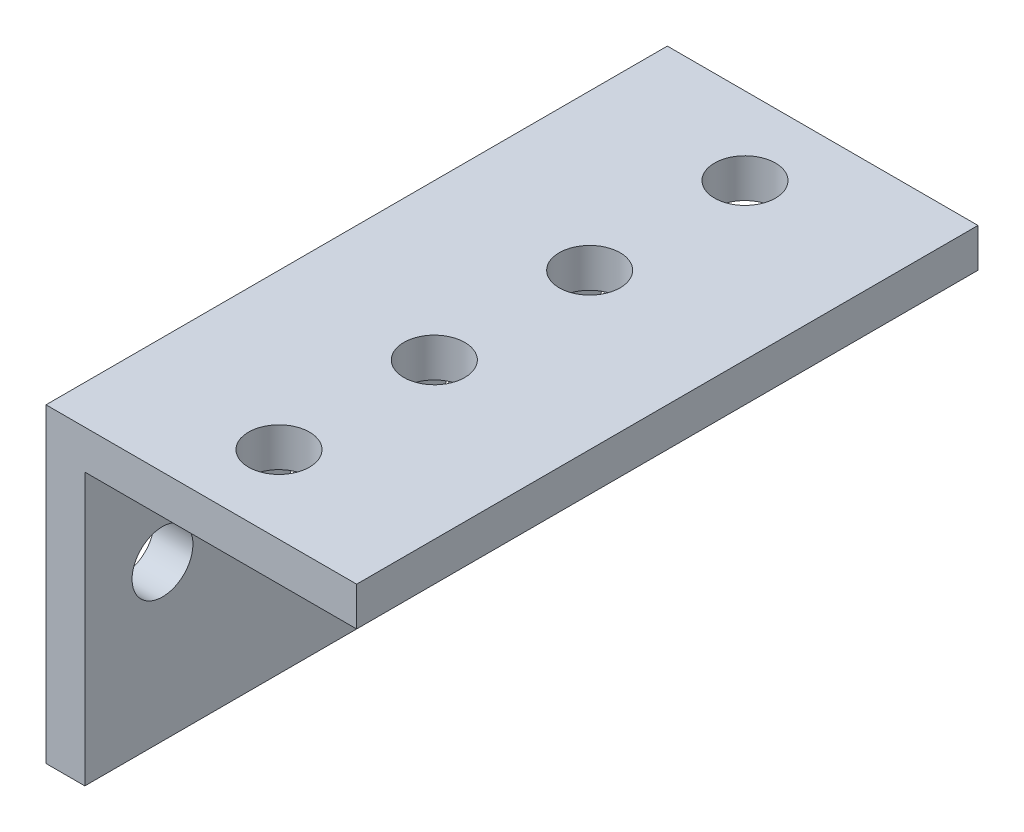
SolidWorks part; units mm, degrees
ref_plane "Front Plane" through (0, 0, 0) normal (0, 0, 1) x (1, 0, 0)
ref_plane "Top Plane" through (0, 0, 0) normal (0, 1, 0) x (1, 0, 0)
ref_plane "Right Plane" through (0, 0, 0) normal (1, 0, 0) x (0, 0, -1)
sketch "Sketch2" plane through (0, 0, 0) normal (0, 0, 1) x (1, 0, 0)
  line L0 (0, 0) -> (0, -25.4)
  line L1 (0, -25.4) -> (3.175, -25.4)
  line L2 (3.175, -25.4) -> (3.175, -3.175)
  line L3 (3.175, -3.175) -> (25.4, -3.175)
  line L4 (25.4, -3.175) -> (25.4, 0)
  line L5 (25.4, 0) -> (0, 0)
  dimension "D1" = 3.175
  dimension "D2" = 25.4
  dimension "D3" = 25.4
extrude "Boss-Extrude1" add sketch "Sketch2" along normal blind 50.8
sketch "Sketch5" plane through (3.175, 0, 0) normal (1, 0, 0) x (0, 0, -1)
  line L0 (-50.8, -25.4) -> (0, -25.4) construction
  line L1 (0, -25.4) -> (0, -3.175) construction
  circle A1 centre (-6.35, -12.7) radius 2.4892
  circle A2 centre (-19.05, -12.7) radius 2.4892
  circle A3 centre (-31.75, -12.7) radius 2.4892
  circle A4 centre (-44.45, -12.7) radius 2.4892
  point P1 (-18.5814, -12.7)
  dimension "D1" = 4.9784
  dimension "D2" = 12.7
  dimension "D3" = 6.35
  dimension "D4" = 4
  dimension "D5" = 12.7
extrude "Cut-Extrude1" cut sketch "Sketch5" against normal through all
sketch "Sketch6" plane through (0, -3.175, 0) normal (0, -1, 0) x (1, 0, 0)
  line L0 (3.175, 0) -> (25.4, 0) construction
  line L1 (25.4, 50.8) -> (25.4, 0) construction
  circle A0 centre (12.7, 6.35) radius 2.4892
  circle A1 centre (12.7, 19.05) radius 2.4892
  circle A2 centre (12.7, 31.75) radius 2.4892
  circle A3 centre (12.7, 44.45) radius 2.4892
  dimension "D3" = 4.9784
  dimension "D1" = 6.35
  dimension "D2" = 12.7
  dimension "D5" = 12.7
  dimension "D4" = 4
extrude "Cut-Extrude2" cut sketch "Sketch6" against normal through all
